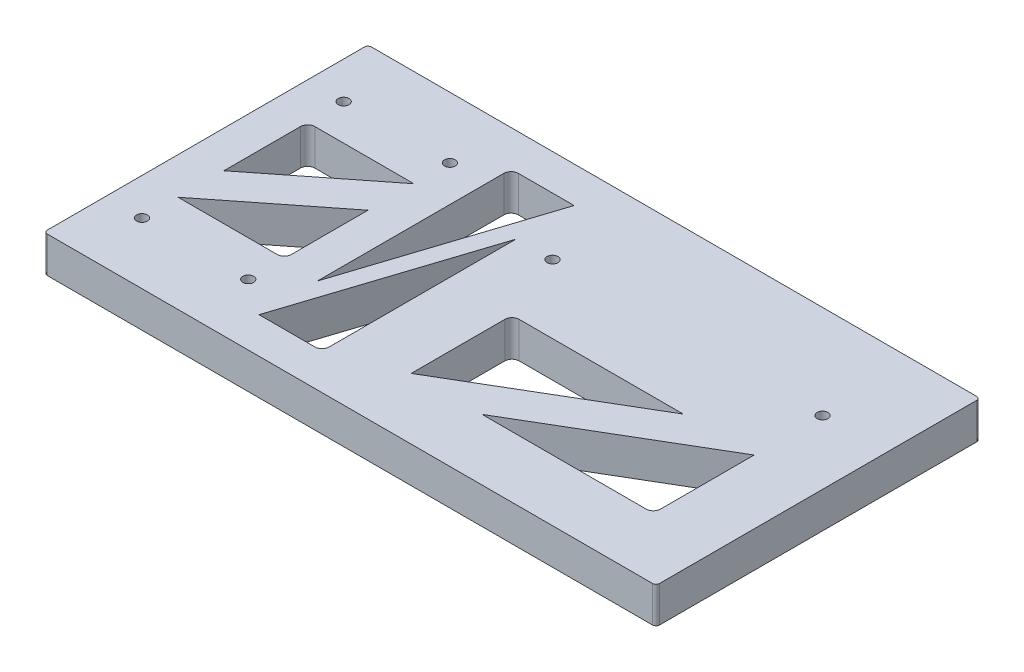
SolidWorks part; units mm, degrees
ref_plane "Front Plane" through (0, 0, 0) normal (0, 0, 1) x (1, 0, 0)
ref_plane "Top Plane" through (0, 0, 0) normal (0, 1, 0) x (1, 0, 0)
ref_plane "Right Plane" through (0, 0, 0) normal (1, 0, 0) x (0, 0, -1)
sketch "Sketch1" plane through (0, 0, 0) normal (0, 1, 0) x (1, 0, 0)
  line L1 (85, -45) -> (-85, -45)
  line L2 (85, -45) -> (85, 45)
  line L3 (85, 45) -> (-85, 45)
  line L4 (-85, -45) -> (-85, 45)
  line L5 (85, -45) -> (-85, 45) construction
  line L6 (85, 45) -> (-85, -45) construction
  point P0 (0, 0)
  dimension "D1" = 170
  dimension "D2" = 90
extrude "Boss-Extrude1" add sketch "Sketch1" along normal blind 10
sketch "Sketch2" plane through (0, 10, 0) normal (0, 1, 0) x (1, 0, 0)
  line L0 (-85, 45) -> (-85, -45) construction
  line L5 (-60, -28) -> (-60, 0) construction
  line L7 (0, 0) -> (-85, 0) construction
  line L12 (-74.75, -28) -> (-45.25, -28) construction
  circle A0 centre (-7.75, 19) radius 1.5
  circle A1 centre (67.25, 19) radius 1.5
  circle A2 centre (-74.75, -28) radius 1.5
  circle A3 centre (-45.25, -28) radius 1.5
  point P0 (-60, -28)
  point P3 (-60, -28)
  dimension "D6" = 19
  dimension "D8" = 3
  dimension "D2" = 3
  dimension "D1" = 29.5
  dimension "D3" = 28
  dimension "D4" = 25
  dimension "D5" = 52.25
  dimension "D7" = 75
extrude "Cut-Extrude1" cut sketch "Sketch2" against normal through all contours A2 | A3 region at (-74.75, 10, 28) region at (-45.25, 10, 28)
mirror "Mirror1" about plane through (0, 0, 0) normal (0, 0, 1) of "Cut-Extrude1"
fillet "Fillet1" radius 1 4 edges at (-85, 5, -45) (85, 5, -45) (85, 5, 45) (-85, 5, 45)
extrude "Cut-Extrude2" cut sketch "Sketch2<9>" against normal through all contours A1 | A0 region at (-7.75, 10, -19) region at (67.25, 10, -19)
sketch "Sketch2<9>" plane through (0, 10, 0) normal (0, 1, 0) x (1, 0, 0) same geometry as "Sketch2"
sketch "Sketch3" plane through (0, 10, 0) normal (0, 1, 0) x (1, 0, 0)
  line L1 (-45.25, -28) -> (0, -28) construction
  line L3 (67.25, 19) -> (67.25, 0) construction
  line L6 (0, -28) -> (47.5441, 0)
  line L7 (19.7059, -28) -> (67.25, 0)
  line L8 (0, -28) -> (19.7059, -28)
  line L9 (47.5441, 0) -> (67.25, 0)
  line L10 (84, 45) -> (-84, 45) construction
  line L11 (0, -28) -> (67.25, -28)
  line L12 (0, -28) -> (0, 0)
  line L13 (0, 0) -> (67.25, 0)
  line L14 (67.25, -28) -> (67.25, 0)
  line L15 (33.625, 0) -> (33.625, -28) construction
  line L16 (0, -14) -> (67.25, -14) construction
  line L17 (-17.75, -35) -> (-35.25, -35)
  line L18 (-17.75, -35) -> (-17.75, 35)
  line L19 (-17.75, 35) -> (-35.25, 35)
  line L20 (-35.25, -35) -> (-35.25, 35)
  line L21 (-26.5, 35) -> (-26.5, -35) construction
  line L22 (-17.75, 0) -> (-35.25, 0) construction
  line L23 (-35.25, -35) -> (-17.75, 18.8282)
  line L24 (-35.25, -18.8282) -> (-17.75, 35)
  line L25 (-45.25, -28) -> (-45.25, -18) construction
  line L26 (-45.25, -18) -> (-74.75, -18)
  line L27 (-45.25, -18) -> (-45.25, 18)
  line L28 (-45.25, 18) -> (-74.75, 18)
  line L29 (-74.75, -18) -> (-74.75, 18)
  line L30 (-60, 18) -> (-60, -18) construction
  line L31 (-45.25, 0) -> (-74.75, 0) construction
  line L32 (-74.75, 28) -> (-74.75, 18) construction
  line L33 (-74.75, -18) -> (-45.25, 5.2645)
  line L34 (-74.75, -5.2645) -> (-45.25, 18)
  circle A0 centre (-7.75, 19) radius 1.5 construction
  point P178 (-26.5, 0)
  point P206 (33.625, -14)
  point P455 (-60, 0)
  dimension "D1" = 10
  dimension "D2" = 10
  dimension "D3" = 10
  dimension "D4" = 10
  dimension "D5" = 5
  dimension "D6" = 10
  dimension "D7" = 10
extrude "Cut-Extrude3" cut sketch "Sketch3" against normal through all contours L6 | L7 | L17 L18 | L20 L19 | L29 L34 L28 | L33 L26 L27 region at (15.848, 10, 9.3333) region at (51.402, 10, 18.6667) region at (-23.5833, 10, 17.0573) region at (-29.4167, 10, -17.0573) region at (-55.0833, 10, 10.2452) region at (-64.9167, 10, -10.2452)
fillet "Fillet3" radius 2 6 edges at (-17.75, 5, 35) (-35.25, 5, -35) (67.25, 5, 28) (0, 5, 0) (-74.75, 5, -18) (-45.25, 5, 18)
